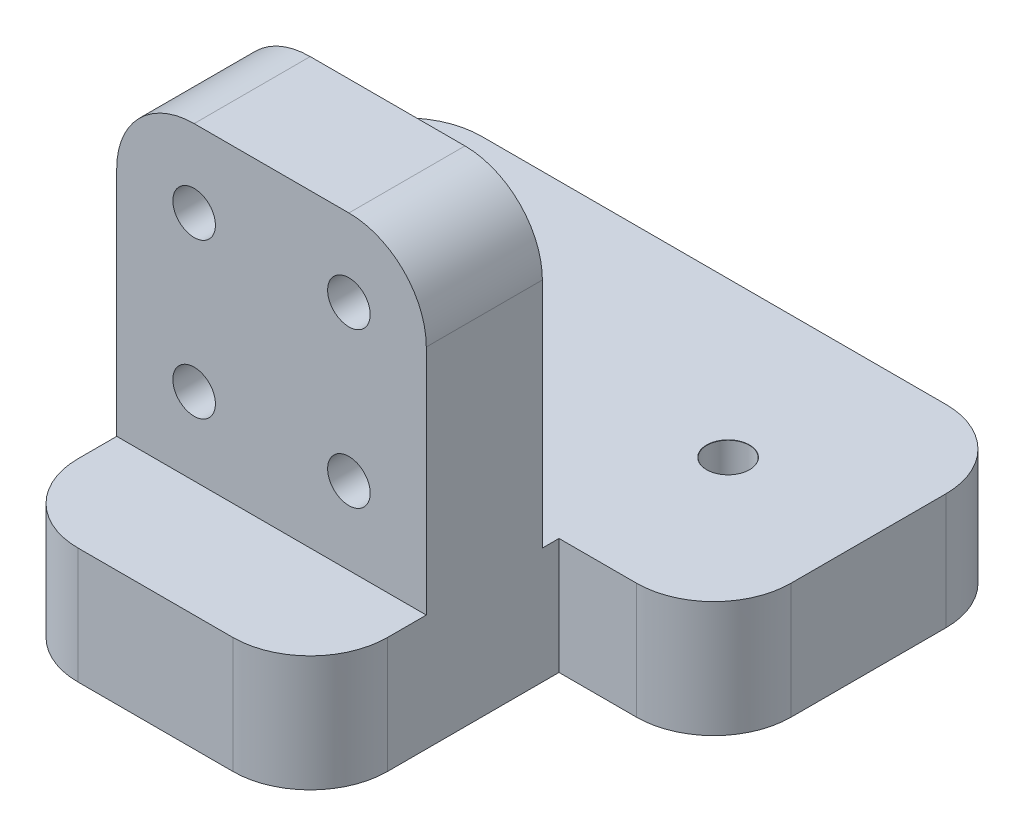
SolidWorks part; units mm, degrees
ref_plane "Front Plane" through (0, 0, 0) normal (0, 0, 1) x (1, 0, 0)
ref_plane "Top Plane" through (0, 0, 0) normal (0, 1, 0) x (1, 0, 0)
ref_plane "Right Plane" through (0, 0, 0) normal (1, 0, 0) x (0, 0, -1)
sketch "Sketch1" plane through (0, 0, 0) normal (0, 1, 0) x (1, 0, 0)
  line L1 (0, 0) -> (40, 0)
  line L7 (40, 0) -> (40, 32.15)
  line L8 (0, 0) -> (0, 32.15)
  line L13 (0, 32.15) -> (-20, 32.15)
  line L14 (-20, 32.15) -> (-20, 72.15)
  line L15 (-20, 72.15) -> (60, 72.15)
  line L16 (60, 72.15) -> (60, 32.15)
  line L17 (60, 32.15) -> (40, 32.15)
  line L18 (-1.85, 52.15) -> (41.85, 52.15) construction
  point P1 (41.85, 52.15)
  point P12 (-1.85, 52.15)
  point P13 (-20, 52.15)
  point P16 (20, 72.15)
  point P17 (20, 52.15)
  point P25 (0, 0)
  dimension "D1" = 40
  dimension "D2" = 52.15
  dimension "D3" = 40
  dimension "D4" = 43.7
  dimension "D5" = 20
extrude "Boss-Extrude1" add sketch "Sketch1" along normal blind 15 contours L1 region at (20, 0, -41.8084)
sketch "Sketch6" plane through (0, 15, 0) normal (0, 1, 0) x (1, 0, 0)
  point P0 (-1.85, 52.15)
  point P3 (41.85, 52.15)
hole_wizard "M5 Clearance Hole1" positions "Sketch6" profile "Sketch5" hole size "M5" standard "ANSI Metric" end condition through all
sketch "Sketch5" plane through (-1.85, 15, -52.15) normal (1, 0, 0) x (0, 0, 1)
  line L0 (0, 0) -> (0, 15)
  line L1 (0, 15) -> (2.75, 15)
  line L2 (2.75, 15) -> (2.75, 0.025)
  line L3 (2.75, 0.025) -> (2.775, 0)
  line L5 (2.775, 0) -> (0, 0)
  line L6 (-2.75, 0.025) -> (-2.775, 0) construction
  line L11 (0, -6.35) -> (0, 107.95) construction
  dimension "Thru Hole Dia." = 5.5
  dimension "Thru Hole Depth" = 15
  dimension "Near C'Sink Dia." = 5.55
  dimension "Near C'Sink Angle" = 90
sketch "Sketch8" plane through (0, 15, 0) normal (0, 1, 0) x (1, 0, 0)
  line L0 (0, 0) -> (0, 32.15) construction
  line L1 (0, 15) -> (40, 15)
  line L2 (0, 15) -> (0, 30)
  line L3 (0, 30) -> (40, 30)
  line L4 (40, 15) -> (40, 30)
  line L5 (40, 0) -> (40, 32.15) construction
  line L6 (0, 0) -> (40, 0) construction
  dimension "D1" = 15
  dimension "D2" = 15
extrude "Boss-Extrude2" add sketch "Sketch8" along normal blind 40
sketch "Sketch11" plane through (0, 0, -30) normal (0, 0, -1) x (-1, 0, 0)
  line L1 (-30, 45) -> (-10, 45) construction
  line L2 (-30, 45) -> (-30, 25) construction
  line L3 (-30, 25) -> (-10, 25) construction
  line L4 (-10, 45) -> (-10, 25) construction
  line L5 (-40, 55) -> (0, 55) construction
  line L6 (-40, 55) -> (-40, 15) construction
  point P1 (-30, 45)
  point P2 (-10, 25)
  point P85 (-30, 25)
  point P86 (-10, 45)
  point P93 (-30, 45)
  point P95 (-10, 45)
  point P103 (-30, 25)
  point P105 (-10, 25)
  point P110 (-20, 55)
  point P111 (-20, 45)
  point P114 (-40, 35)
  point P115 (-30, 35)
  dimension "D1" = 20
hole_wizard "M5 Clearance Hole2" positions "Sketch11" profile "Sketch10" hole size "M5" standard "ANSI Metric" end condition through all
sketch "Sketch10" plane through (10, 25, -30) normal (1, 0, 0) x (0, 1, 0)
  line L0 (0, 0) -> (0, 30)
  line L1 (0, 30) -> (2.75, 30)
  line L2 (2.75, 30) -> (2.75, 0.025)
  line L3 (2.75, 0.025) -> (2.775, 0)
  line L5 (2.775, 0) -> (0, 0)
  line L6 (-2.75, 0.025) -> (-2.775, 0) construction
  line L11 (0, -6.35) -> (0, 107.95) construction
  dimension "Thru Hole Dia." = 5.5
  dimension "Thru Hole Depth" = 30
  dimension "Near C'Sink Dia." = 5.55
  dimension "Near C'Sink Angle" = 90
fillet "Fillet2" radius 10 8 edges at (40, 55, -22.5) (0, 55, -22.5) (-20, 7.5, -32.15) (0, 7.5, 0) (40, 7.5, 0) (60, 7.5, -32.15) (60, 7.5, -72.15) (-20, 7.5, -72.15) first distance on face at (40, 21.25, -19.2875) first distance on face at (0, 21.25, -19.2875) first distance on face at (-10, 7.5, -32.15) first distance on face at (20, 7.5, 0) first distance on face at (50, 7.5, -32.15) first distance on face at (20, 7.5, -72.15)
